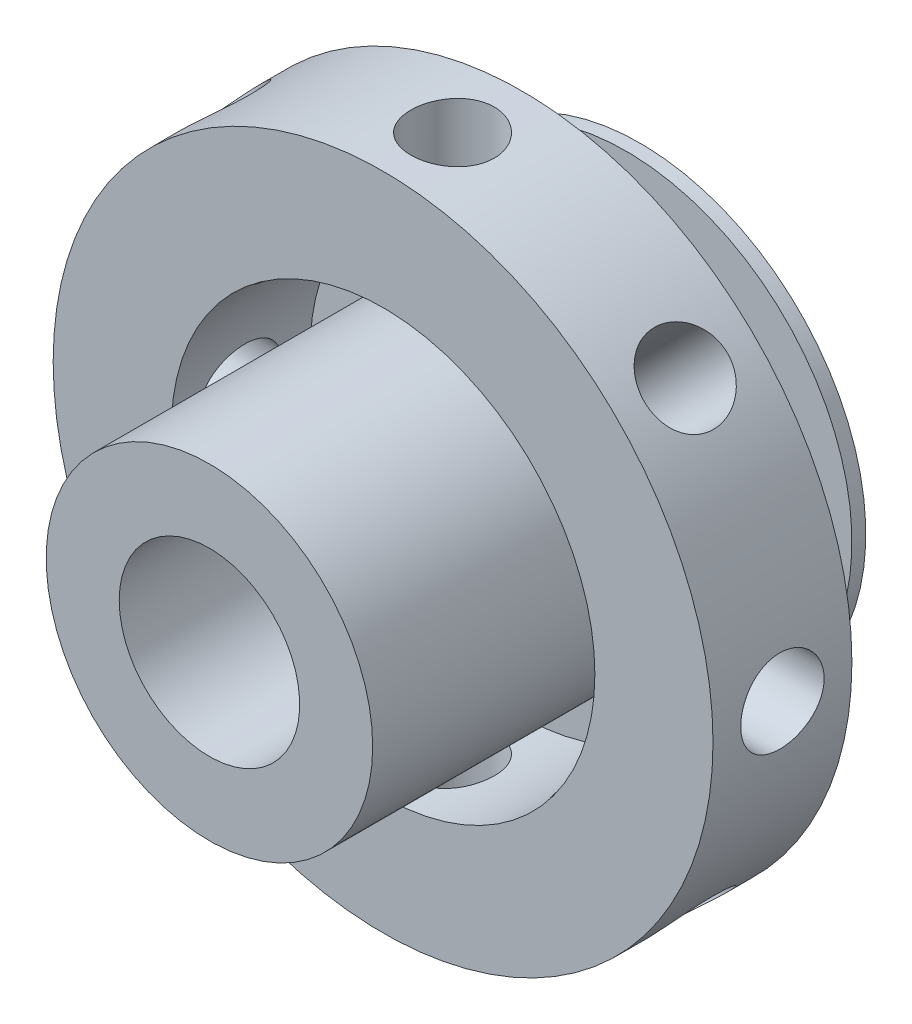
SolidWorks part; units mm, degrees
ref_plane "Alzado" through (0, 0, 0) normal (0, 0, 1) x (1, 0, 0)
ref_plane "Planta" through (0, 0, 0) normal (0, 1, 0) x (1, 0, 0)
ref_plane "Vista lateral" through (0, 0, 0) normal (1, 0, 0) x (0, 0, -1)
sketch "Croquis2" plane through (0, 0, 0) normal (0, 0, 1) x (1, 0, 0)
  circle A0 centre (0, 0) radius 5.97
  dimension "D1" = 11.94
extrude "Saliente-Extruir1" add sketch "Croquis2" against normal blind 10.16
sketch "Croquis3" plane through (0, 0, -10.16) normal (0, 0, -1) x (-1, 0, 0)
  circle A0 centre (0, 0) radius 12.065
  dimension "D1" = 24.13
extrude "Saliente-Extruir2" add sketch "Croquis3" against normal blind 5.08
sketch "Croquis5" plane through (0, 0, -5.08) normal (0, 0, 1) x (1, 0, 0)
  circle A0 centre (0, 0) radius 5.97
  circle A1 centre (0, 0) radius 7.745
  dimension "D1" = 15.49
  dimension "D2" = 11.94
extrude "Cortar-Extruir1" cut sketch "Croquis5" against normal blind 5.08
sketch "Croquis6" plane through (0, 0, -10.16) normal (0, 0, -1) x (-1, 0, 0)
  circle A0 centre (0, 0) radius 9.525
  dimension "D1" = 19.05
extrude "Saliente-Extruir3" add sketch "Croquis6" along normal blind 1.27
fillet "Redondeo1" radius 1.27 1 edges at (9.525, 0, -10.16)
sketch "Croquis7" plane through (0, 0, -11.43) normal (0, 0, -1) x (-1, 0, 0)
  circle A0 centre (0, 0) radius 4.445
  dimension "D1" = 8.89
extrude "Saliente-Extruir4" add sketch "Croquis7" along normal blind 2.54
sketch "Croquis8" plane through (0, 0, -13.97) normal (0, 0, -1) x (-1, 0, 0)
  circle A0 centre (0, 0) radius 8.255
  dimension "D1" = 16.51
extrude "Saliente-Extruir5" add sketch "Croquis8" along normal blind 1.27
chamfer "Chaflán1" distance 0.762 angle 71 1 edges at (-8.255, 0, -15.24) first distance on face at (-8.255, 0, -15.24)
sketch "Croquis9" plane through (0, 0, -15.24) normal (0, 0, -1) x (-1, 0, 0)
  circle A0 centre (0, 0) radius 3.3
  dimension "D1" = 6.6
extrude "Cortar-Extruir2" cut sketch "Croquis9" against normal blind 19.05
ref_plane "Plano1" through (0, 12.065, 0) normal (0, 1, 0) x (1, 0, 0)
sketch "Croquis10" plane through (0, 12.065, 0) normal (0, 1, 0) x (1, 0, 0)
  line L0 (0, 10.16) -> (0, 5.08) construction
  line L1 (12.065, 10.16) -> (-12.065, 10.16) construction
  line L2 (-12.065, 5.08) -> (12.065, 5.08) construction
  circle A0 centre (0, 7.62) radius 1.525
  dimension "D1" = 3.05
extrude "Cortar-Extruir3" cut sketch "Croquis10" against normal blind 5.08
ref_axis "Eje1" through (0, 0, -10.16) along (0, 0, 1)
pattern_circular "MatrizC1" count 8 every 45 about axis through (0, 0, -10.16) along (0, 0, 1) of "Cortar-Extruir3"
sketch "Croquis11" plane through (0, 0, 0) normal (0, 0, 1) x (1, 0, 0)
  circle A0 centre (0, 0) radius 3.3
  circle A1 centre (0, 0) radius 5.97
  dimension "D1" = 11.94
  dimension "D2" = 6.6
extrude "Saliente-Extruir6" add sketch "Croquis11" along normal blind 1.27
